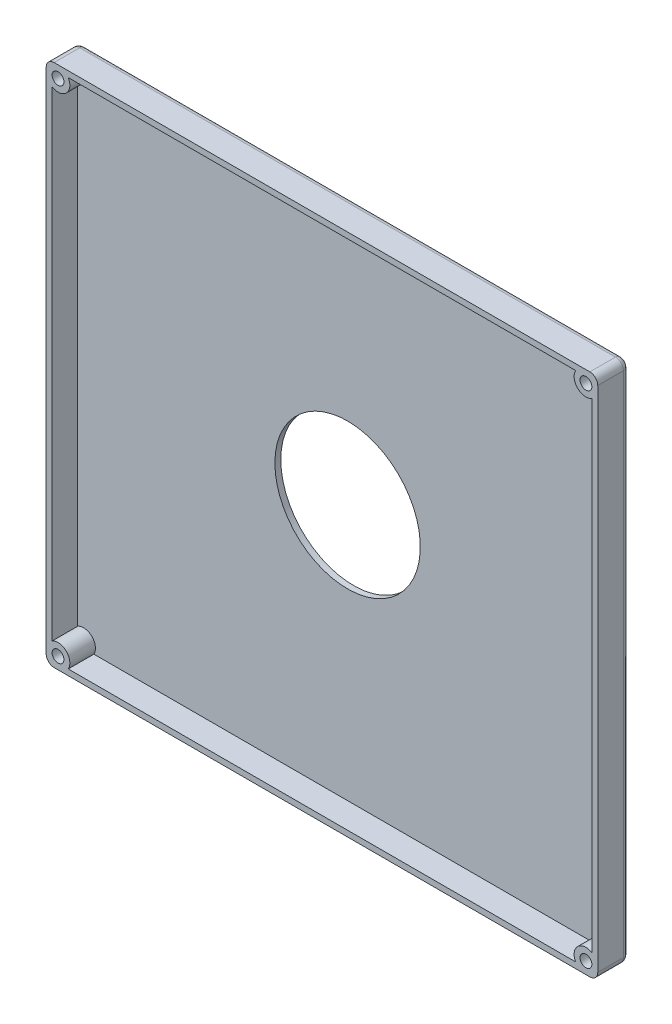
SolidWorks part; units mm, degrees
ref_plane "Front Plane" through (0, 0, 0) normal (0, 0, 1) x (1, 0, 0)
ref_plane "Top Plane" through (0, 0, 0) normal (0, 1, 0) x (1, 0, 0)
ref_plane "Right Plane" through (0, 0, 0) normal (1, 0, 0) x (0, 0, -1)
sketch "Sketch1" plane through (0, 0, 0) normal (0, 0, 1) x (1, 0, 0)
  line L1 (-70, -66.5) -> (70, -66.5)
  line L2 (-70, -66.5) -> (-70, 66.5)
  line L3 (-70, 66.5) -> (70, 66.5)
  line L4 (70, -66.5) -> (70, 66.5)
  line L5 (-70, -66.5) -> (70, 66.5) construction
  line L6 (-70, 66.5) -> (70, -66.5) construction
  point P0 (0, 0)
  dimension "D1" = 140
  dimension "D2" = 133
extrude "Boss-Extrude1" add sketch "Sketch1" along normal blind 8
hole_wizard "Ø3.0 (3) Diameter Hole1" positions "Sketch11" profile "Sketch12" hole size "Ø3.0" standard "AS" end condition through all
sketch "Sketch11" plane through (0, 0, 8) normal (0, 0, 1) x (1, 0, 0)
  line L0 (-70, 66.5) -> (-70, -66.5) construction
  line L1 (70, 66.5) -> (-70, 66.5) construction
  line L2 (70, -66.5) -> (70, 66.5) construction
  line L3 (-70, -66.5) -> (70, -66.5) construction
  point P0 (-67, 63.5)
  point P8 (67, 63.5)
  point P13 (-67, -63.5)
  point P15 (67, -63.5)
  dimension "D1" = 3
  dimension "D2" = 3
  dimension "D3" = 3
  dimension "D4" = 3
  dimension "D5" = 3
  dimension "D6" = 3
  dimension "D7" = 3
  dimension "D8" = 3
sketch "Sketch12" plane through (-67, 63.5, 8) normal (1, 0, 0) x (0, -1, 0)
  line L0 (0, 0) -> (0, 8)
  line L1 (0, 8) -> (1.5, 8)
  line L2 (1.5, 8) -> (1.5, 0)
  line L5 (1.5, 0) -> (0, 0)
  line L11 (0, -6.35) -> (0, 107.95) construction
  dimension "Thru Hole Dia." = 3
  dimension "Thru Hole Depth" = 8
shell "Shell3" thickness 1.5 removed face at (-65.5, 63.5, 8)
fillet "Fillet2" radius 2 1 edges at (-70, 66.5, 4) type face fillet first side face at (0, 66.5, 4) second side face at (-70, 0, 4)
fillet "Fillet3" radius 2 1 edges at (-70, -66.5, 4) type face fillet first side face at (-70, -1, 4) second side face at (0, -66.5, 4)
fillet "Fillet4" radius 2 1 edges at (70, -66.5, 4) type face fillet first side face at (1, -66.5, 4) second side face at (70, 0, 4)
fillet "Fillet5" radius 2 1 edges at (70, 66.5, 4) type face fillet first side face at (70, 1, 4) second side face at (1, 66.5, 4)
sketch "Sketch13" plane through (0, 0, 0) normal (0, 0, -1) x (-1, 0, 0)
  circle A0 centre (0, 0) radius 18.4549
extrude "Cut-Extrude1" cut sketch "Sketch13" against normal blind 10
fillet "Fillet6" radius 1.5 1 edges at (70, 0, 0) type face fillet first side face at (70, 0, 4) second side face at (-18.4549, 0, 0)
